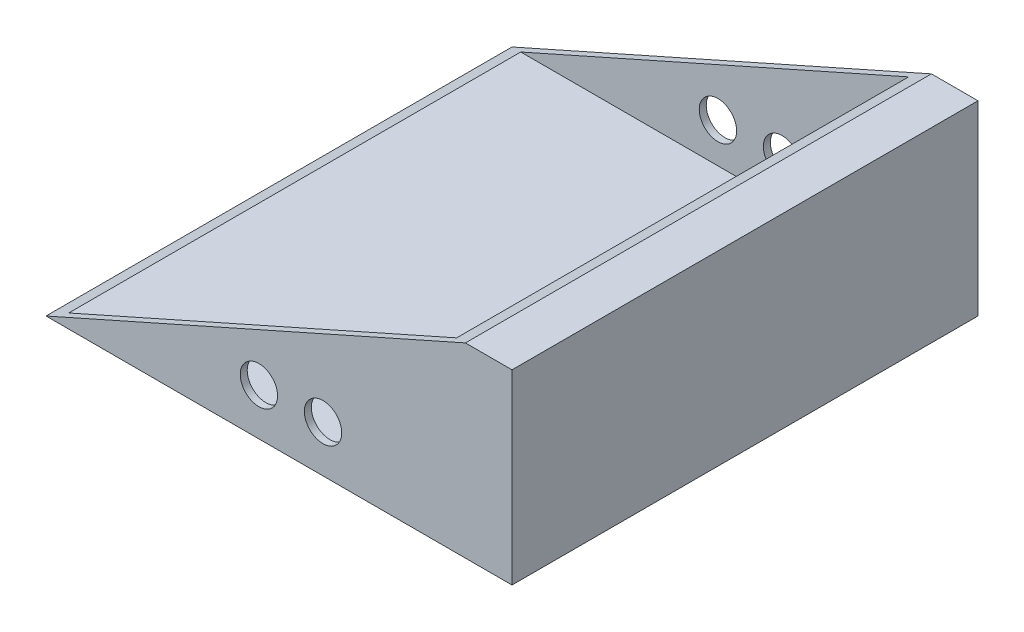
SolidWorks part; units mm, degrees
ref_plane "Front Plane" through (0, 0, 0) normal (0, 0, 1) x (1, 0, 0)
ref_plane "Top Plane" through (0, 0, 0) normal (0, 1, 0) x (1, 0, 0)
ref_plane "Right Plane" through (0, 0, 0) normal (1, 0, 0) x (0, 0, -1)
sketch "Sketch1" plane through (0, 0, 0) normal (0, 0, 1) x (1, 0, 0)
  line L3 (0, 0) -> (200, 0)
  line L4 (200, 0) -> (200, 80)
  line L5 (200, 80) -> (180, 80)
  line L6 (180, 80) -> (0, 0)
  dimension "D1" = 80
  dimension "200" = 200
  dimension "D2" = 20
  dimension "D3" = 196.9772
extrude "Boss-Extrude4" add sketch "Sketch1" along normal blind 200
shell "Shell2" thickness 3 removed face at (90, 40, 100)
sketch "Sketch3" plane through (0, 80, 0) normal (0, 1, 0) x (1, 0, 0)
  line L0 (200, 0) -> (200, -200) construction
  line L1 (200, -100) -> (0, -100) construction
  line L2 (0, -200) -> (0, 0) construction
sketch "Sketch4" plane through (0, 0, 200) normal (0, 0, 1) x (1, 0, 0)
  line L0 (0, 0) -> (200, 0) construction
  circle A0 centre (91.379, 20) radius 8.02
  circle A1 centre (118.899, 20) radius 8.02
  point P6 (117.086, 20)
  dimension "D1" = 20
  dimension "16.04" = 16.04
  dimension "D2" = 16.04
  dimension "D3" = 20
  dimension "D4" = 27.52
extrude "Boss-Extrude5" add sketch "Sketch4" against normal blind 3
extrude "Cut-Extrude1" cut sketch "Sketch4<7>" against normal blind 4
sketch "Sketch4<7>" plane through (0, 0, 200) normal (0, 0, 1) x (1, 0, 0) same geometry as "Sketch4"
sketch "Sketch5" plane through (0, 0, 0) normal (0, 0, 1) x (1, 0, 0)
  circle A0 centre (91.379, 20) radius 8.02
  circle A1 centre (118.899, 20) radius 8.02
  point P6 (117.086, 20)
  dimension "16.04" = 16.04
  dimension "D2" = 16.04
  dimension "D4" = 27.52
extrude "Cut-Extrude2" cut sketch "Sketch5" along normal blind 4 contours A0 | A1
